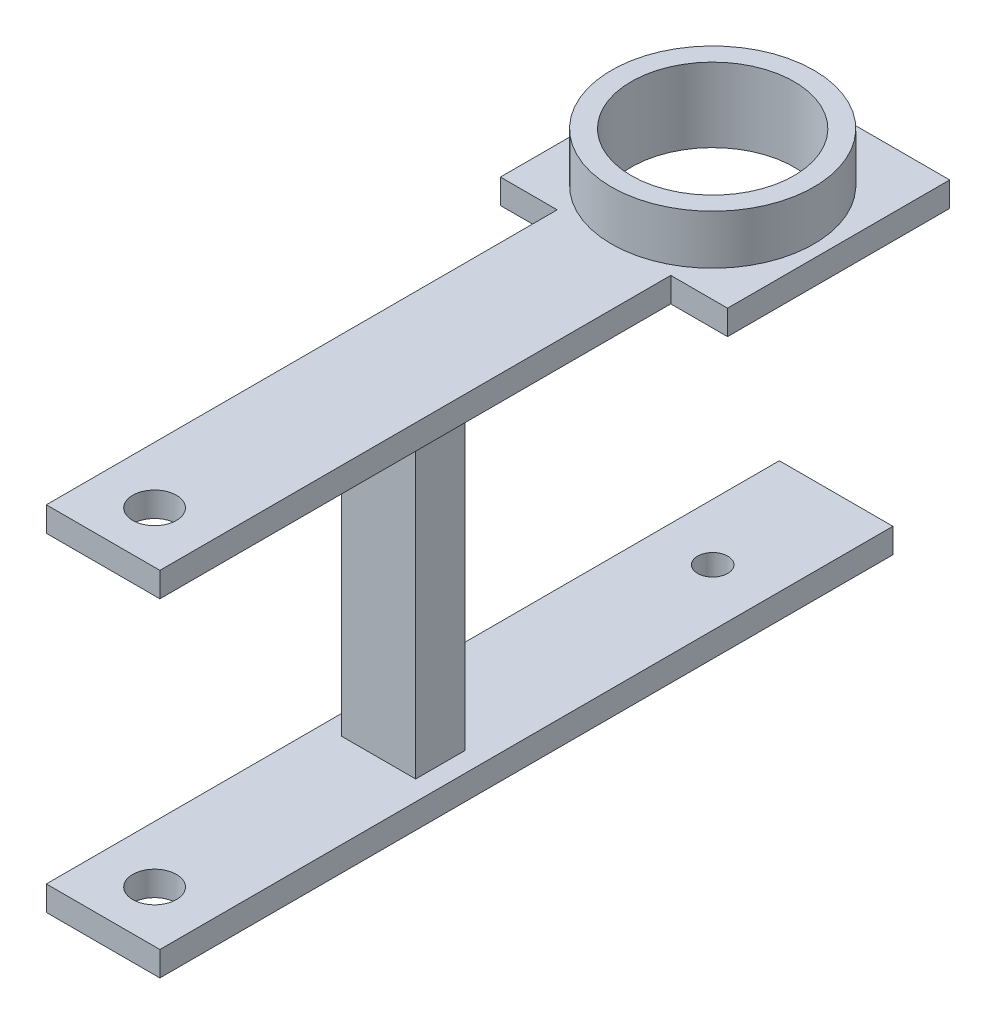
SolidWorks part; units mm, degrees
ref_plane "Front Plane" through (0, 0, 0) normal (0, 0, 1) x (1, 0, 0)
ref_plane "Top Plane" through (0, 0, 0) normal (0, 1, 0) x (1, 0, 0)
ref_plane "Right Plane" through (0, 0, 0) normal (1, 0, 0) x (0, 0, -1)
sketch "Sketch1" plane through (0, 0, 0) normal (0, 1, 0) x (1, 0, 0)
  line L0 (0, 0) -> (0, -63.9421) construction
  line L1 (-23, 0) -> (23, 0)
  line L2 (0, 0) -> (0, -135)
  line L3 (-23, -135) -> (23, -135)
  line L4 (23, 0) -> (23, -135)
  line L5 (-23, 0) -> (-23, -135)
  line L6 (43.6695, 0) -> (-43.6695, 0) construction
  line L7 (-23, 0) -> (-23, 25)
  line L8 (23, 0) -> (23, 25)
  line L9 (-23, 25) -> (23, 25)
  line L10 (0, 0) -> (0, -113.03) construction
  circle A0 centre (0, 0) radius 3.05
  circle A1 centre (0, -113.03) radius 4.425
  point P11 (0, 0)
  dimension "D1" = 6.1
  dimension "D6" = 8.85
  dimension "D2" = 23
  dimension "D3" = 135
  dimension "D4" = 25
  dimension "D5" = 113.03
extrude "Boss-Extrude2" add sketch "Sketch1" along normal blind 5 contours A0 L1 L5 L3 L2 | A0 L2 L3 L4 L1 | A0 L1 L8 L9 L7 region at (0, 0, -12.6442) region at (11.6208, 0, 67.2011) region at (-11.6208, 0, 67.2011)
sketch "Sketch2" plane through (23, 0, 0) normal (1, 0, 0) x (0, 0, -1)
  line L0 (-135, 5) -> (-135, 0) construction
  line L1 (25, 5) -> (-135, 5)
  line L2 (25, 5) -> (25, 71.5)
  line L3 (25, 71.5) -> (-135, 71.5)
  line L4 (-135, 5) -> (-135, 71.5)
  dimension "D1" = 66.5
sketch "Sketch3" plane through (0, 0, 135) normal (0, 0, 1) x (1, 0, 0)
  line L0 (-23, 5) -> (-23, 71.5)
  dimension "D1" = 66.5
ref_plane "Plane1" through (0, 71.5, 0) normal (0, 1, 0) x (1, 0, 0)
sketch "Sketch4" plane through (0, 71.5, 0) normal (0, 1, 0) x (1, 0, 0)
  line L1 (23, 25) -> (-23, 25)
  line L2 (23, 25) -> (23, -135)
  line L3 (23, -135) -> (-23, -135)
  line L4 (-23, 25) -> (-23, -135)
extrude "Boss-Extrude3" add sketch "Sketch4" against normal blind 5 separate body
sketch "Sketch5" plane through (0, 71.5, 0) normal (0, 1, 0) x (1, 0, 0)
  circle A0 centre (0, 0) radius 16.5
  circle A1 centre (0, 0) radius 20.5
  dimension "D1" = 33
  dimension "D2" = 4
extrude "Cut-Extrude2" cut sketch "Sketch5" against normal blind 5 contours A0 region at (0, 71.5, 0)
extrude "Boss-Extrude5" add sketch "Sketch5<6>" along normal blind 10
sketch "Sketch5<6>" plane through (0, 71.5, 0) normal (0, 1, 0) x (1, 0, 0) same geometry as "Sketch5"
sketch "Sketch7" plane through (0, 5, 0) normal (0, 1, 0) x (1, 0, 0)
  line L0 (0, -113.03) -> (0, -62.65) construction
  line L1 (0, -62.65) -> (-23, -62.65) construction
  line L2 (-23, 25) -> (-23, -135) construction
  line L3 (-23, -62.65) -> (23, -62.65) construction
  line L4 (23, 25) -> (23, -135) construction
  line L5 (-23, -67.65) -> (-7.5, -67.65)
  line L6 (23, -67.65) -> (7.5, -67.65)
  line L7 (7.5, -67.65) -> (7.5, -62.65) construction
  line L8 (-7.5, -57.65) -> (7.5, -57.65)
  line L9 (-7.5, -67.65) -> (7.5, -67.65)
  line L10 (-7.5, -67.65) -> (-7.5, -57.65)
  line L11 (-7.5, -62.65) -> (7.5, -62.65)
  line L12 (7.5, -67.65) -> (7.5, -57.65)
  line L14 (-23, -135) -> (23, -135) construction
  circle A0 centre (0, -62.65) radius 3
  dimension "D2" = 6
  dimension "D1" = 50.38
  dimension "D3" = 15.5
  dimension "D4" = 5
  dimension "D5" = 21.97
extrude "Boss-Extrude7" add sketch "Sketch7" along normal up to surface (61.5 mm away) contours A0 L11 L12 L8 L10 | A0 L11 L10 L9 L12 | L11 A0 | L11 A0 region at (0, 5, 57.8081) region at (-5.25, 5, 62.8081) region at (0, 5, 61.3768) region at (0, 5, 63.9232) up to face at (0, 66.5, 16.5)
sketch "Sketch8" plane through (0, 5, 0) normal (0, 1, 0) x (1, 0, 0)
  line L0 (7.5, -67.65) -> (11.5, -67.65) construction
  line L1 (-7.5, -67.65) -> (-11.5, -67.65)
  line L3 (11.5, -67.65) -> (23, -67.65)
  line L4 (11.5, -67.65) -> (11.5, -135)
  line L5 (11.5, -135) -> (23, -135)
  line L6 (23, -67.65) -> (23, -135)
  line L7 (11.5, -67.65) -> (23, -67.65)
  line L8 (11.5, -67.65) -> (11.5, 25)
  line L9 (11.5, 25) -> (23, 25)
  line L10 (23, -67.65) -> (23, 25)
  line L11 (-11.5, -67.65) -> (-23, -67.65)
  line L12 (-11.5, -67.65) -> (-11.5, -135)
  line L13 (-11.5, -135) -> (-23, -135)
  line L14 (-23, -67.65) -> (-23, -135)
  line L15 (-11.5, -67.65) -> (-23, -67.65)
  line L16 (-11.5, -67.65) -> (-11.5, 25)
  line L17 (-11.5, 25) -> (-23, 25)
  line L18 (-23, -67.65) -> (-23, 25)
  line M7 (23, -135) -> (23, 25)
  line M8 (23, 25) -> (-23, 25)
  line M9 (-23, 25) -> (-23, -135)
  line M10 (-23, -135) -> (23, -135)
  dimension "D1" = 4
  dimension "D2" = 4
extrude "Cut-Extrude3" cut sketch "Sketch8" against normal blind 10 contours L12 L11 M9 M10 | L11 L16 M8 M9 | L3 L4 M10 M7 | L8 L3 M7 M8 region at (17.25, 5, 21.325) region at (17.25, 5, 101.325) region at (-17.25, 5, 101.325) region at (-17.25, 5, 21.325)
sketch "Sketch10" plane through (0, 66.5, 0) normal (0, -1, 0) x (1, 0, 0)
  line L0 (0, 16.5) -> (0, 19.9874) construction
  line L1 (23, 19.9874) -> (-23, 19.9874) construction
  line L10 (-23, -25) -> (-23, 135) construction
  line L12 (-23, 19.9874) -> (-11.5, 19.9874)
  line L13 (-23, 19.9874) -> (-23, 135)
  line L14 (-23, 135) -> (-11.5, 135)
  line L15 (-11.5, 19.9874) -> (-11.5, 135)
  line L16 (23, 19.9874) -> (11.5, 19.9874)
  line L17 (23, 19.9874) -> (23, 135)
  line L18 (23, 135) -> (11.5, 135)
  line L19 (11.5, 19.9874) -> (11.5, 135)
  circle A0 centre (0, 0) radius 16.5 construction
  point P11 (0, 19.9874)
extrude "Cut-Extrude5" cut sketch "Sketch10" against normal blind 10
sketch "Sketch11" plane through (0, 66.5, 0) normal (0, -1, 0) x (1, 0, 0)
  circle A0 centre (0, 113.03) radius 4.425
extrude "Cut-Extrude6" cut sketch "Sketch11" against normal blind 10
sketch "Sketch12" plane through (0, 5, 0) normal (0, 1, 0) x (1, 0, 0)
  line L0 (0, -117.455) -> (0, -123.455) construction
  line L2 (0, -123.455) -> (-11.5, -123.455)
  line L3 (0, -123.455) -> (0, -135)
  line L4 (0, -135) -> (-11.5, -135)
  line L5 (-11.5, -123.455) -> (-11.5, -135)
  line L6 (0, -123.455) -> (11.5, -123.455)
  line L7 (0, -123.455) -> (0, -135)
  line L8 (0, -135) -> (11.5, -135)
  line L9 (11.5, -123.455) -> (11.5, -135)
  circle A0 centre (0, -113.03) radius 4.425 construction
  line M9 (-11.5, 25) -> (-11.5, -135)
  line M10 (-11.5, -135) -> (11.5, -135)
  line M11 (11.5, -135) -> (11.5, 25)
  dimension "D1" = 6
extrude "Cut-Extrude7" cut sketch "Sketch12" against normal blind 10 contours L3 L2 M9 M10 | L6 L3 M10 M11 region at (-5.75, 5, 129.2275) region at (5.75, 5, 129.2275)
sketch "Sketch13" plane through (0, 71.5, 0) normal (0, 1, 0) x (1, 0, 0)
  line L0 (0, -117.455) -> (0, -123.455) construction
  line L2 (0, -123.455) -> (-11.5, -123.455)
  line L3 (0, -123.455) -> (0, -135)
  line L4 (0, -135) -> (-11.5, -135)
  line L5 (-11.5, -123.455) -> (-11.5, -135)
  line L6 (0, -123.455) -> (11.5, -123.455)
  line L7 (0, -123.455) -> (0, -135)
  line L8 (0, -135) -> (11.5, -135)
  line L9 (11.5, -123.455) -> (11.5, -135)
  circle A0 centre (0, -113.03) radius 4.425 construction
  line M4 (-11.5, -19.9874) -> (-11.5, -135)
  line M5 (-11.5, -135) -> (11.5, -135)
  line M6 (11.5, -135) -> (11.5, -19.9874)
  dimension "D1" = 6
extrude "Cut-Extrude8" cut sketch "Sketch13" against normal blind 10 contours L3 L2 M4 M5 | L6 L3 M5 M6 region at (-5.75, 71.5, 129.2275) region at (5.75, 71.5, 129.2275)
